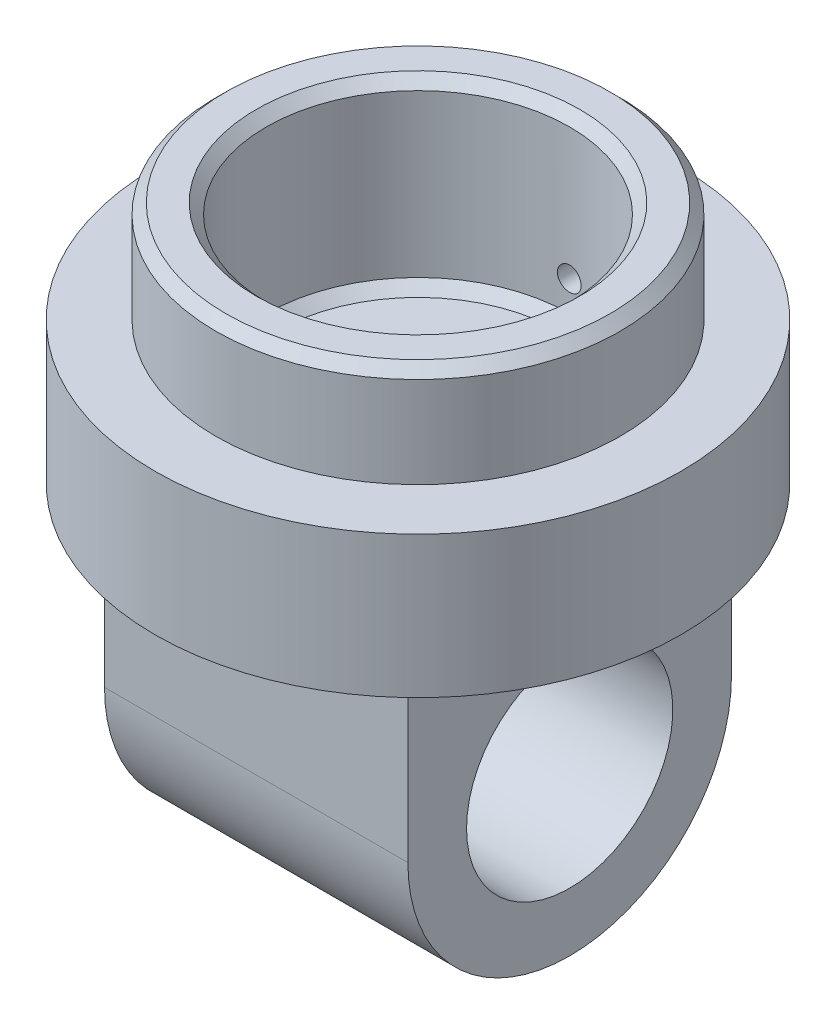
SolidWorks part; units mm, degrees
ref_plane "Front Plane" through (0, 0, 0) normal (0, 0, 1) x (1, 0, 0)
ref_plane "Top Plane" through (0, 0, 0) normal (0, 1, 0) x (1, 0, 0)
ref_plane "Right Plane" through (0, 0, 0) normal (1, 0, 0) x (0, 0, -1)
sketch "Sketch1" plane through (0, 0, 0) normal (0, 1, 0) x (1, 0, 0)
  circle A0 centre (0, 0) radius 13
  dimension "D1" = 26
extrude "Boss-Extrude1" add sketch "Sketch1" along normal blind 7
sketch "Sketch2" plane through (0, 7, 0) normal (0, 1, 0) x (1, 0, 0)
  circle A0 centre (0, 0) radius 10
  dimension "D1" = 20
extrude "Boss-Extrude2" add sketch "Sketch2" along normal blind 5
sketch "Sketch3" plane through (0, 12, 0) normal (0, 1, 0) x (1, 0, 0)
  circle A0 centre (0, 0) radius 7.5
  dimension "D1" = 15
extrude "Cut-Extrude1" cut sketch "Sketch3" against normal blind 9
chamfer "Chamfer1" distance 0.5 angle 45 3 edges at (0, 12, 10) (0, 3, 7.5) (0, 12, 7.5)
sketch "Sketch4" plane through (0, 0, 0) normal (0, 0, 1) x (1, 0, 0)
  circle A0 centre (0, 5) radius 0.585
  dimension "D1" = 1.17
  dimension "D2" = 5
extrude "Cut-Extrude2" cut sketch "Sketch4" against normal through all
sketch "Sketch5" plane through (0, 0, 0) normal (0, -1, 0) x (1, 0, 0)
  line L1 (-7.5, -8) -> (7.5, -8)
  line L2 (-7.5, -8) -> (-7.5, 8)
  line L3 (-7.5, 8) -> (7.5, 8)
  line L4 (7.5, -8) -> (7.5, 8)
  line L5 (-7.5, -8) -> (7.5, 8) construction
  line L6 (-7.5, 8) -> (7.5, -8) construction
  point P0 (0, 0)
  dimension "D1" = 15
  dimension "D2" = 16
extrude "Boss-Extrude3" add sketch "Sketch5" along normal blind 16.5
fillet "Fillet1" radius 8 2 edges at (0, -16.5, 8) (0, -16.5, -8)
sketch "Sketch8" plane through (-7.5, 0, 0) normal (-1, 0, 0) x (0, 0, 1)
  circle A0 centre (0, -8.5) radius 5.1
  dimension "D1" = 10.2
  dimension "D2" = 8.5
extrude "Cut-Extrude4" cut sketch "Sketch8" against normal up to surface (15 mm away) up to face at (7.5, -7.3627, 0)
ref_plane "Plane1" through (0, 0, -13) normal (0, 0, -1) x (-1, 0, 0)
sketch "Sketch9" plane through (0, 0, -13) normal (0, 0, -1) x (-1, 0, 0)
  circle A0 centre (0, 5) radius 1.17
  dimension "D1" = 2.34
extrude "Cut-Extrude5" cut sketch "Sketch9" against normal blind 1
equation "\"pin_bore\"=10.20"
equation "\"top_outer_diameter\"=16.00"
equation "\"D1@Sketch8\"=\"pin_bore\""
equation "\"D1@Boss-Extrude3\"=\"bottom_height\""
equation "\"bottom_height\"=16.50"
equation "\"D2@Sketch5\"=\"top_outer_diameter\""
equation "\"D1@Fillet1\"=\"top_outer_diameter\"/2"
equation "\"bottom_bore_height\"=8.50"
equation "\"D2@Sketch8\"=\"bottom_bore_height\""
equation "\"valve_diameter\"=1.17"
equation "\"D1@Sketch4\"=\"valve_diameter\""
equation "\"D1@Sketch9\"=\"valve_diameter\"*2"
